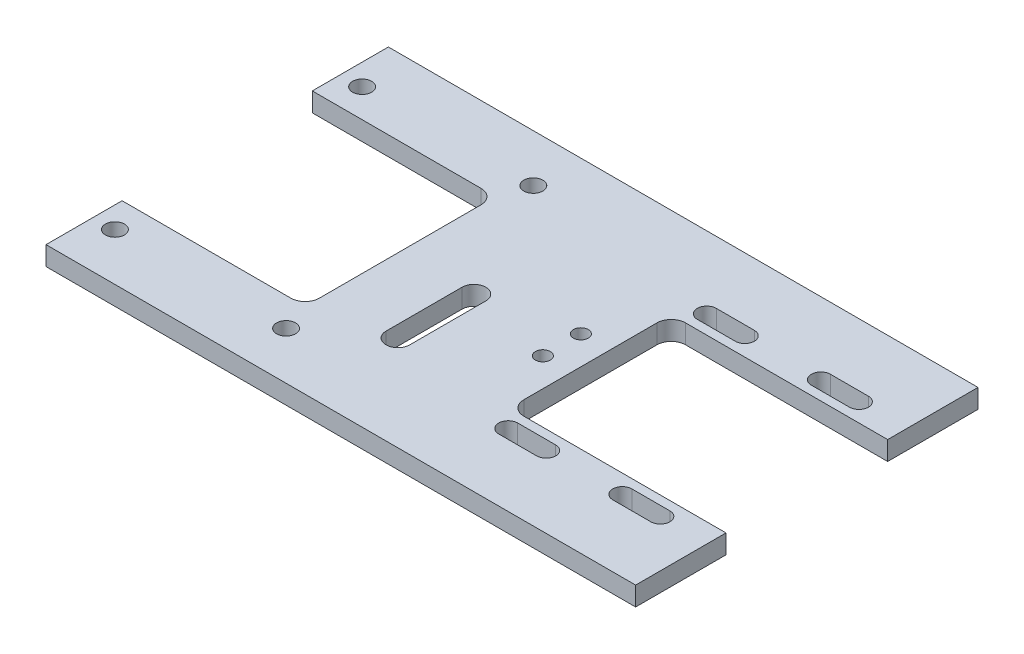
SolidWorks part; units mm, degrees
material "6061-T6 (SS)"
ref_plane "Front Plane" through (0, 0, 0) normal (0, 0, 1) x (1, 0, 0)
ref_plane "Top Plane" through (0, 0, 0) normal (0, 1, 0) x (1, 0, 0)
ref_plane "Right Plane" through (0, 0, 0) normal (1, 0, 0) x (0, 0, -1)
sketch "Sketch1" plane through (0, 0, 0) normal (0, 1, 0) x (1, 0, 0)
  line L0 (0, 0) -> (50000, 0) construction
  line L5 (-7.125, 57.15) -> (-7.125, -57.15)
  line L6 (-7.125, 57.15) -> (189.725, 57.15)
  line L7 (189.725, 57.15) -> (189.725, -57.15)
  line L8 (0, 41.275) -> (0, 0) construction
  line L9 (189.725, -57.15) -> (-7.125, -57.15)
  line L10 (0, 41.275) -> (57.15, 41.275) construction
  circle A0 centre (0, 41.275) radius 3.175
  circle A5 centre (0, -41.275) radius 3.175
  circle A10 centre (57.15, 41.275) radius 3.175
  circle A11 centre (57.15, -41.275) radius 3.175
  point P25 (152.8, 0)
  point P29 (-7.125, 0)
  dimension "D1" = 6.35
  dimension "D3" = 7.125
  dimension "D7" = 196.85
  dimension "D11" = 57.15
  dimension "D12" = 57.15
  dimension "D2" = 41.275
extrude "Boss-Extrude1" add sketch "Sketch1" along normal blind 6.35
sketch "Sketch2" plane through (0, 6.35, 0) normal (0, 1, 0) x (1, 0, 0)
  line L1 (-7.125, 0) -> (-7.125, -31.75)
  line L2 (189.725, 0) -> (-7.125, 0) construction
  line L3 (-7.125, 57.15) -> (-7.125, -57.15) construction
  line L7 (189.725, -57.15) -> (189.725, 57.15) construction
  line L8 (-7.125, -31.75) -> (53.975, -31.75)
  line L9 (53.975, -31.75) -> (53.975, 0)
  line L10 (53.975, 0) -> (53.975, 31.75)
  line L11 (53.975, 31.75) -> (-7.125, 31.75)
  line L12 (-7.125, 31.75) -> (-7.125, 0)
  circle A1 centre (57.15, 41.275) radius 3.175 construction
  dimension "D3" = 3.175
  dimension "D4" = 31.75
extrude "Cut-Extrude1" cut sketch "Sketch2" against normal up to next contours L10 L11 L12 L1 L8 L9
sketch "Sketch3" plane through (0, 6.35, 0) normal (0, 1, 0) x (1, 0, 0)
  line L0 (53.975, 0) -> (189.725, 0) construction
  line L1 (53.975, -31.75) -> (53.975, 31.75) construction
  line L3 (62.725, 57.15) -> (62.725, -57.15) construction
  line L4 (189.725, 57.15) -> (-7.125, 57.15) construction
  line L5 (-7.125, -57.15) -> (189.725, -57.15) construction
  line L6 (-7.125, 57.15) -> (-7.125, 31.75) construction
  line L7 (189.725, -57.15) -> (189.725, 57.15) construction
  dimension "D1" = 69.85
sketch "Sketch7" plane through (0, 0, 0) normal (0, -1, 0) x (1, 0, 0)
  line L0 (189.725, 57.15) -> (189.725, -57.15) construction
  line L4 (53.975, 31.75) -> (53.975, -31.75) construction
  line L5 (53.975, 0) -> (117.475, 0) construction
  line L8 (117.475, -26.9875) -> (189.725, -26.9875)
  line L9 (117.475, -26.9875) -> (117.475, 26.9875)
  line L10 (117.475, 26.9875) -> (189.725, 26.9875)
  line L11 (189.725, -26.9875) -> (189.725, 26.9875)
  dimension "D2" = 63.5
  dimension "D5" = 53.975
extrude "Cut-Extrude3" cut sketch "Sketch7" against normal blind 6.35 contours L11 L10 L9 | L8 L11 region at (153.6, 0, 0)
sketch "Sketch9" plane through (0, 6.35, 0) normal (0, 1, 0) x (1, 0, 0)
  line L0 (0, 0) -> (189.725, 0) construction
  line L1 (129.525, -33.147) -> (167.625, -33.147) construction
  line L2 (148.575, -33.147) -> (148.575, -26.9875) construction
  line L3 (117.475, -26.9875) -> (189.725, -26.9875) construction
  line L4 (78.6, 0) -> (78.6, -25.4) construction
  line L5 (189.725, 26.9875) -> (189.725, 57.15) construction
  line L6 (135.875, -33.147) -> (123.175, -33.147) construction
  line L7 (135.875, -36.322) -> (123.175, -36.322)
  line L8 (135.875, -29.972) -> (123.175, -29.972)
  line L9 (161.275, -33.147) -> (173.975, -33.147) construction
  line L10 (161.275, -29.972) -> (173.975, -29.972)
  line L11 (161.275, -36.322) -> (173.975, -36.322)
  line L12 (161.275, 33.147) -> (173.975, 33.147) construction
  line L13 (161.275, 29.972) -> (173.975, 29.972)
  line L14 (161.275, 36.322) -> (173.975, 36.322)
  line L15 (135.875, 33.147) -> (123.175, 33.147) construction
  line L16 (135.875, 36.322) -> (123.175, 36.322)
  line L17 (135.875, 29.972) -> (123.175, 29.972)
  line L19 (0, -41.275) -> (57.15, -41.275) construction
  line L20 (28.575, -41.275) -> (28.575, -108.3593) construction
  line L21 (82.5687, 0) -> (82.5687, -25.4)
  line L22 (74.6312, 0) -> (74.6312, -25.4)
  line L23 (-7.125, -31.75) -> (-7.125, -57.15) construction
  arc A0 (135.875, -36.322) -> (135.875, -29.972) centre (135.875, -33.147) ccw
  arc A1 (123.175, -29.972) -> (123.175, -36.322) centre (123.175, -33.147) ccw
  arc A2 (161.275, -29.972) -> (161.275, -36.322) centre (161.275, -33.147) ccw
  arc A3 (173.975, -36.322) -> (173.975, -29.972) centre (173.975, -33.147) ccw
  arc A4 (161.275, 29.972) -> (161.275, 36.322) centre (161.275, 33.147) cw
  arc A5 (173.975, 36.322) -> (173.975, 29.972) centre (173.975, 33.147) cw
  arc A6 (135.875, 36.322) -> (135.875, 29.972) centre (135.875, 33.147) cw
  arc A7 (123.175, 29.972) -> (123.175, 36.322) centre (123.175, 33.147) cw
  arc A9 (82.5687, 0) -> (74.6312, 0) centre (78.6, 0) ccw
  arc A10 (74.6312, -25.4) -> (82.5687, -25.4) centre (78.6, -25.4) ccw
  point P15 (129.525, -33.147)
  point P22 (167.625, -33.147)
  point P31 (167.625, 33.147)
  point P38 (129.525, 33.147)
  point P51 (78.6, -12.7)
  dimension "D7" = 7.9375
  dimension "D8" = 85.725
  dimension "D4" = 3.175
  dimension "D6" = 12.7
  dimension "D1" = 66.294
  dimension "D2" = 38.1
  dimension "D3" = 120
  dimension "D5" = 12.7
  dimension "D9" = 25.4
extrude "Cut-Extrude4" cut sketch "Sketch9" against normal blind 6.35 contours L8 A1 L7 A0 | L11 A3 L10 A2 | A5 L14 A4 L13 | A7 L17 A6 L16 | L22 A10 L21 A9
fillet "Fillet1" radius 4.7625 4 edges at (53.975, 3.175, 31.75) (53.975, 3.175, -31.75) (117.475, 3.175, 26.9875) (117.475, 3.175, -26.9875)
sketch "Sketch10" plane through (0, 6.35, 0) normal (0, 1, 0) x (1, 0, 0)
  line L0 (117.475, 0) -> (111.125, 0) construction
  line L1 (117.475, 22.225) -> (117.475, -22.225) construction
  line L3 (104.775, -9.525) -> (117.475, -9.525) construction
  line L4 (104.775, -9.525) -> (104.775, 9.525) construction
  line L5 (104.775, 9.525) -> (117.475, 9.525) construction
  line L6 (117.475, -9.525) -> (117.475, 9.525) construction
  line L7 (104.775, -9.525) -> (117.475, 9.525) construction
  line L8 (104.775, 9.525) -> (117.475, -9.525) construction
  line L9 (104.775, -9.525) -> (107.95, -9.525) construction
  line L10 (104.775, -9.525) -> (104.775, -6.35) construction
  line L11 (104.775, -6.35) -> (107.95, -6.35) construction
  line L12 (107.95, -9.525) -> (107.95, -6.35) construction
  line L13 (104.775, -9.525) -> (107.95, -6.35) construction
  line L14 (104.775, -6.35) -> (107.95, -9.525) construction
  line L15 (104.775, 9.525) -> (107.95, 9.525) construction
  line L16 (104.775, 9.525) -> (104.775, 6.35) construction
  line L17 (104.775, 6.35) -> (107.95, 6.35) construction
  line L18 (107.95, 9.525) -> (107.95, 6.35) construction
  line L19 (104.775, 9.525) -> (107.95, 6.35) construction
  line L20 (104.775, 6.35) -> (107.95, 9.525) construction
  circle A0 centre (107.95, -6.35) radius 2.4892
  circle A1 centre (107.95, 6.35) radius 2.4892
  point P12 (106.3625, -7.9375)
  point P16 (106.3625, 7.9375)
  dimension "D1" = 4.9784
  dimension "D2" = 9.525
  dimension "D3" = 6.35
extrude "Cut-Extrude5" cut sketch "Sketch10" against normal blind 6.35
